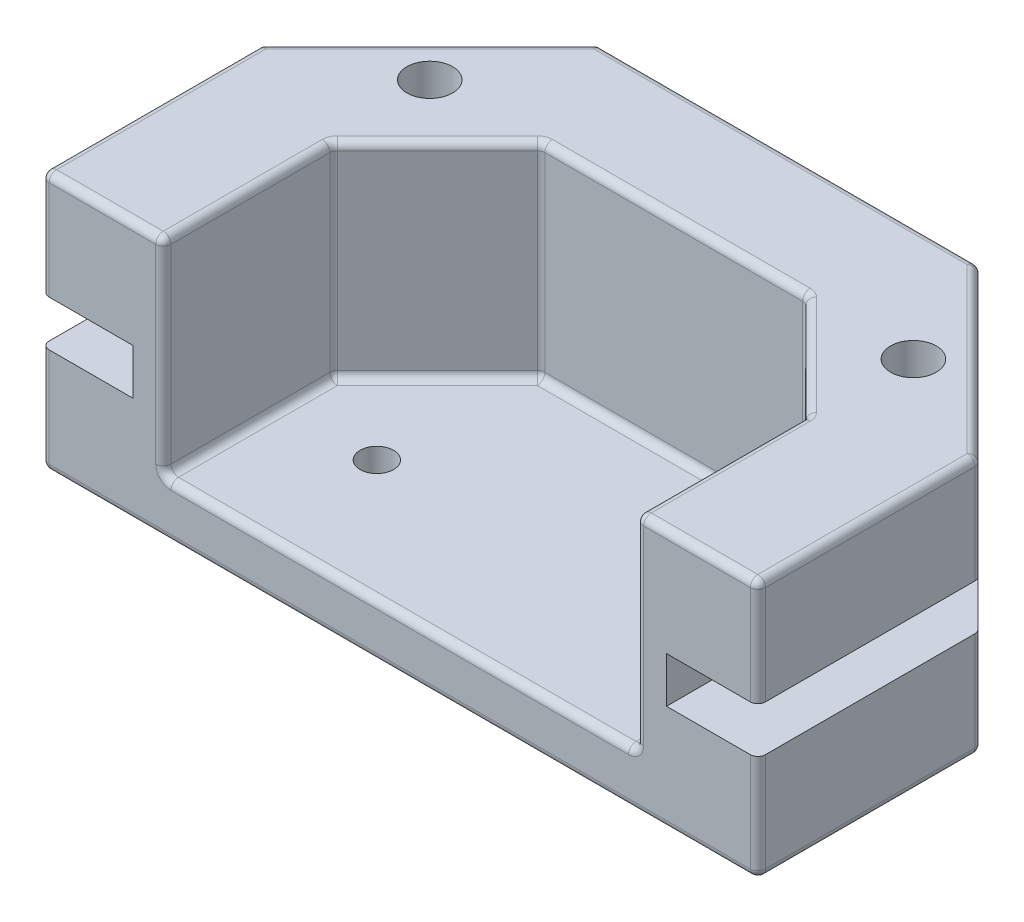
SolidWorks part; units mm, degrees
ref_plane "Front Plane" through (0, 0, 0) normal (0, 0, 1) x (1, 0, 0)
ref_plane "Top Plane" through (0, 0, 0) normal (0, 1, 0) x (1, 0, 0)
ref_plane "Right Plane" through (0, 0, 0) normal (1, 0, 0) x (0, 0, -1)
ref_plane "Motor Holder Bottom" through (0, -3.5, 0) normal (0, -1, 0) x (-1, 0, 0)
sketch "Sketch1" plane through (0, 0, 0) normal (0, 1, 0) x (1, 0, 0)
  line L7 (27.4734, -52.5) -> (21.4734, -52.5)
  line L13 (29.4734, -52.5) -> (60.5266, -52.5)
  line L16 (27.4734, -52.5) -> (27.4734, -40.5266)
  line L18 (60.5266, -52.5) -> (62.5266, -52.5)
  line L19 (55, -33) -> (62.5266, -40.5266)
  line L20 (27.4734, -40.5266) -> (35, -33)
  line L21 (62.5266, -40.5266) -> (62.5266, -52.5)
  line L22 (35, -33) -> (55, -33)
  line L23 (29.4734, -52.5) -> (29.4734, -41.3551)
  line L25 (29.4734, -41.3551) -> (36.3284, -34.5)
  line L26 (36.3284, -34.5) -> (53.6716, -34.5)
  line L27 (53.6716, -34.5) -> (60.5266, -41.3551)
  line L28 (60.5266, -41.3551) -> (60.5266, -52.5)
  line L30 (29.4734, -52.5) -> (27.4734, -52.5)
  line L31 (21.4734, -52.5) -> (21.4734, -38.0413)
  line L32 (21.4734, -38.0413) -> (32.5147, -27)
  line L33 (32.5147, -27) -> (57.4853, -27)
  line L34 (57.4853, -27) -> (68.5266, -38.0413)
  line L35 (68.5266, -38.0413) -> (68.5266, -52.5)
  line L36 (62.5266, -52.5) -> (68.5266, -52.5)
  line L37 (35, -33) -> (55, -33) construction
  line L38 (55, -33) -> (62.5266, -40.5266) construction
  line L39 (62.5266, -40.5266) -> (62.5266, -52.5) construction
  line L40 (35, -33) -> (27.4734, -40.5266) construction
  line L41 (27.4734, -40.5266) -> (27.4734, -52.5) construction
  line L42 (19.9734, -52.5) -> (27.4734, -52.5) construction
  dimension "D1" = 6
  dimension "D4" = 2
  dimension "D5" = 2
  dimension "D6" = 1.5
  dimension "D7" = 2
  dimension "D8" = 2
extrude "Boss-Extrude1" add sketch "Sketch1" along normal blind 10 and the other way blind 7 contours L16 | L16 L18 region at (24.4734, 0, 51.9648) region at (27.8745, 0, 46.5133)
extrude "Boss-Extrude4" add sketch "Sketch1<5>" along normal up to surface (-3.5 mm away) from surface contours L28 L27 L26 L25 L23 L13 region at (45, 0, 44.1163) up to plane "Motor Holder Bottom" starting at face at (45, -7, 40.9827)
sketch "Sketch1<5>" plane through (0, 0, 0) normal (0, 1, 0) x (1, 0, 0) same geometry as "Sketch1"
fillet "Fillet1" radius 0.5 36 edges at (29.4734, 10, 46.9275) (60.5266, 10, 46.9275) (60.5266, -3.5, 46.9275) (29.4734, -3.5, 46.9275) (45, -7, 52.5) (21.4734, 1.5, 52.5) (25.4734, 10, 52.5) (29.4734, 3.25, 52.5) (45, -3.5, 52.5) (60.5266, 3.25, 52.5) (64.5266, 10, 52.5) (68.5266, 1.5, 52.5) (57.0991, 10, 37.9275) (60.5266, 3.25, 41.3551) (57.0991, -3.5, 37.9275) (45, 10, 34.5) (53.6716, 3.25, 34.5) (45, -3.5, 34.5) (32.9009, 10, 37.9275) (36.3284, 3.25, 34.5) (32.9009, -3.5, 37.9275) (29.4734, 3.25, 41.3551) (21.4734, 10, 45.2707) (68.5266, 10, 45.2707) (63.006, 10, 32.5207) (45, 10, 27) (26.994, 10, 32.5207) (21.4734, 1.5, 38.0413) (32.5147, 1.5, 27) (57.4853, 1.5, 27) (68.5266, 1.5, 38.0413) (26.994, -7, 32.5207) (21.4734, -7, 45.2707) (45, -7, 27) (63.006, -7, 32.5207) (68.5266, -7, 45.2707)
extrude "Cut-Extrude1" cut sketch "Sketch1<3>" along normal up to surface (3 mm away) contours L16 region at (24.4734, 0, 51.9648)
sketch "Sketch1<3>" plane through (0, 0, 0) normal (0, 1, 0) x (1, 0, 0) same geometry as "Sketch1"
sketch "Sketch2" plane through (0, 10, 0) normal (0, 1, 0) x (1, 0, 0)
  line L0 (26.994, -32.5207) -> (31.2367, -36.7633) construction
  line L1 (21.4734, -38.0413) -> (32.5147, -27) construction
  line L3 (63.006, -32.5207) -> (58.7633, -36.7633) construction
  line L4 (57.4853, -27) -> (68.5266, -38.0413) construction
  line L6 (35, -33) -> (27.4734, -40.5266) construction
  line L7 (55, -33) -> (62.5266, -40.5266) construction
  circle A0 centre (29.1154, -34.642) radius 1.5
  circle A1 centre (60.8846, -34.642) radius 1.5
  point P4 (0, 0)
  point P5 (0, 0)
  point P10 (0, 0)
  dimension "D1" = 3
  dimension "D2" = 3
extrude "Cut-Extrude2" cut sketch "Sketch2" against normal up to surface (17 mm away) up to face at (45, -7, 39.2495)
sketch "Sketch4" plane through (0, 0, 0) normal (0, 1, 0) x (1, 0, 0)
  circle A0 centre (35.5, -44.5) radius 1.1 construction
  circle A1 centre (35.5, -44.5) radius 1.1
  circle A2 centre (54.5, -44.5) radius 1.1 construction
  circle A3 centre (54.5, -44.5) radius 1.1
extrude "Cut-Extrude3" cut sketch "Sketch4" against normal up to surface (7 mm away) from surface up to face at (29.1154, -7, 36.142) starting at face at (45, -3.5, 42.8541)
